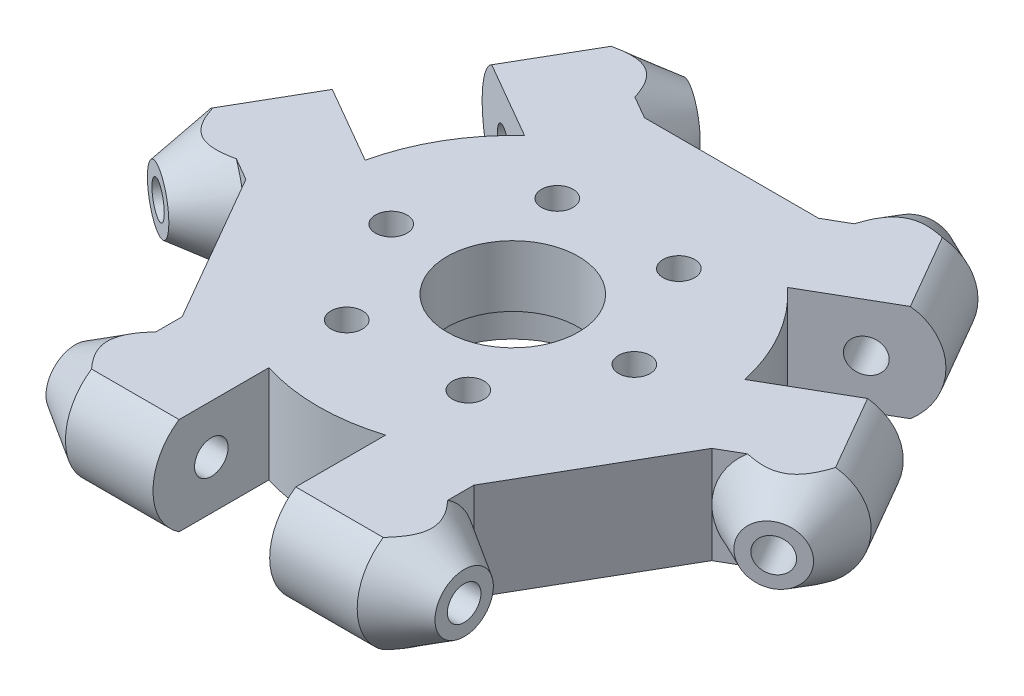
SolidWorks part; units mm, degrees
material "ABS"
ref_plane "Front Plane" through (0, 0, 0) normal (0, 0, 1) x (1, 0, 0)
ref_plane "Top Plane" through (0, 0, 0) normal (0, 1, 0) x (1, 0, 0)
ref_plane "Right Plane" through (0, 0, 0) normal (1, 0, 0) x (0, 0, -1)
sketch "Sketch4" plane through (0, 0, 0) normal (0, 1, 0) x (1, 0, 0)
  line L4 (23.8468, 20.6962) -> (13.5227, 14.7355)
  line L17 (23.8468, 20.6962) -> (19.3468, 28.4904)
  line L18 (19.3468, 28.4904) -> (8.9545, 22.4904)
  line L19 (8.9545, 22.4904) -> (-8.9545, 22.4904)
  line L28 (0, 0) -> (0, 20) construction
  line L29 (0, 0) -> (17.3205, 10) construction
  line L30 (14.1506, 25.4904) -> (30.9357, -3.5822) construction
  line L31 (-23.8468, 20.6962) -> (-13.5227, 14.7355)
  line L32 (-23.8468, 20.6962) -> (-19.3468, 28.4904)
  line L33 (-19.3468, 28.4904) -> (-8.9545, 22.4904)
  line L34 (29.8468, 10.3038) -> (19.5227, 4.3432)
  line L35 (29.8468, 10.3038) -> (34.3468, 2.5096)
  line L36 (34.3468, 2.5096) -> (23.9545, -3.4904)
  line L37 (15, -19) -> (23.9545, -3.4904)
  line L38 (15, -31) -> (15, -19)
  line L39 (6, -31) -> (15, -31)
  line L40 (6, -31) -> (6, -19.0788)
  line L41 (-6, -31) -> (-6, -19.0788)
  line L42 (-6, -31) -> (-15, -31)
  line L43 (-15, -31) -> (-15, -19)
  line L44 (-23.9545, -3.4904) -> (-15, -19)
  line L45 (-34.3468, 2.5096) -> (-23.9545, -3.4904)
  line L46 (-29.8468, 10.3038) -> (-34.3468, 2.5096)
  line L47 (-29.8468, 10.3038) -> (-19.5227, 4.3432)
  arc A0 (-13.5227, 14.7355) -> (-19.5227, 4.3432) centre (0, 0) ccw
  arc A1 (19.5227, 4.3432) -> (13.5227, 14.7355) centre (0, 0) ccw
  arc A2 (-6, -19.0788) -> (6, -19.0788) centre (0, 0) ccw
  circle A9 centre (0, 0) radius 22.4904 construction
  point P67 (0, 0)
  dimension "D2" = 20
  dimension "D8" = 60
  dimension "D12" = 9
  dimension "D13" = 25
  dimension "D14" = 12
  dimension "D9" = 15
  dimension "D15" = 3
extrude "Boss-Extrude1" add sketch "Sketch4" along normal blind 5 and the other way blind 5
sketch "Sketch6" plane through (0, 0, 0) normal (0, 1, 0) x (1, 0, 0)
  line L0 (-15, -25) -> (15, -25) construction
  line L1 (-15, -19) -> (-15, -31) construction
  line L2 (15, -31) -> (15, -19) construction
  line L3 (-15, -25) -> (-20, -25)
  line L4 (-20, -25) -> (-20, -28)
  line L5 (-20, -28) -> (-15, -31)
  line L6 (-15, -31) -> (-15, -25)
  line L7 (0, 0) -> (0, -25) construction
  line L8 (15, -31) -> (15, -25)
  line L9 (20, -28) -> (15, -31)
  line L10 (20, -25) -> (20, -28)
  line L11 (15, -25) -> (20, -25)
  dimension "D1" = 25
  dimension "D2" = 5
  dimension "D3" = 3
revolve "Revolve1" add sketch "Sketch6" angle 360 about L0
pattern_circular "CirPattern1" count 3 over 360 about axis through (0, 5, 0) along (0, 1, 0) of "Revolve1"
sketch "Sketch7" plane through (0, 0, 0) normal (1, 0, 0) x (0, 0, -1)
  line L0 (-28.3166, 5) -> (-19, 5)
  line L1 (-19, 5) -> (-19, 25)
  line L2 (-19, 25) -> (-39, 25)
  line L3 (-39, 25) -> (-39, -25)
  line L4 (-39, -25) -> (-19, -25)
  line L5 (-19, -25) -> (-19, -5)
  line L6 (-19, -5) -> (-28.3166, -5)
  circle A0 centre (-25, 0) radius 1.725
  arc A1 (-28.3166, 5) -> (-28.3166, -5) centre (-25, 0) ccw
  arc A2 (-21.6834, 5) -> (-28.3166, 5) centre (-25, 0) ccw construction
  dimension "D1" = 3.45
  dimension "D2" = 20
  dimension "D3" = 20
  dimension "D4" = 20
extrude "Cut-Extrude2" cut sketch "Sketch7" against normal through all and the other way through all
pattern_circular "CirPattern2" count 3 over 360 about axis through (0, 5, 0) along (0, 1, 0) of "Cut-Extrude2"
sketch "Sketch8" plane through (0, 0, 0) normal (0, 1, 0) x (1, 0, 0)
  circle A0 centre (0, 0) radius 8.5
  circle A1 centre (-12.5, 0) radius 1.625
  circle A2 centre (0, 0) radius 12.5 construction
  circle A3 centre (-6.25, 10.8253) radius 1.625
  circle A4 centre (6.25, 10.8253) radius 1.625
  circle A5 centre (12.5, 0) radius 1.625
  circle A6 centre (6.25, -10.8253) radius 1.625
  circle A7 centre (-6.25, -10.8253) radius 1.625
  point P18 (0, 0)
  dimension "D1" = 17
  dimension "D2" = 3.25
  dimension "D3" = 25
  dimension "D4" = 6
extrude "Cut-Extrude3" cut sketch "Sketch8" against normal through all and the other way through all
sketch "Sketch9" plane through (0, 5, 0) normal (0, 1, 0) x (1, 0, 0)
  circle A0 centre (0, 0) radius 8.5
  circle A1 centre (0, 0) radius 6.75
  circle A2 centre (0, 0) radius 8.5 construction
  point P4 (0, 0)
  dimension "D1" = 13.5
extrude "Boss-Extrude2" add sketch "Sketch9" against normal blind 6.3
